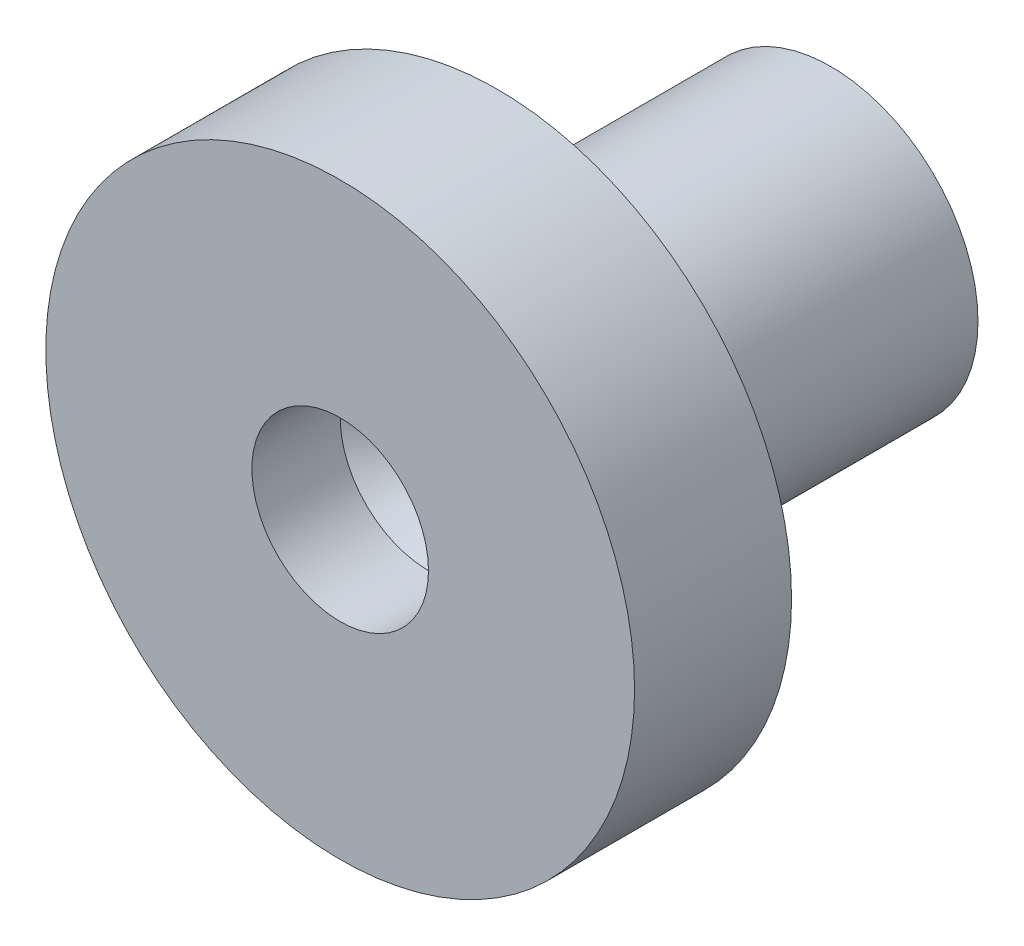
SolidWorks part; units mm, degrees
ref_plane "Спереди" through (0, 0, 0) normal (0, 0, 1) x (1, 0, 0)
ref_plane "Сверху" through (0, 0, 0) normal (0, 1, 0) x (1, 0, 0)
ref_plane "Справа" through (0, 0, 0) normal (1, 0, 0) x (0, 0, -1)
sketch "Эскиз1" plane through (0, 0, 0) normal (0, 0, 1) x (1, 0, 0)
  circle A0 centre (0, 0) radius 4.35
  circle A1 centre (0, 0) radius 7.5
  dimension "D1" = 8.7
  dimension "D2" = 15
extrude "Вытянуть1" add sketch "Эскиз1" along normal blind 17
sketch "Эскиз3" plane through (0, 0, 0) normal (0, 0, -1) x (-1, 0, 0)
  circle A0 centre (0, 0) radius 6
  dimension "D1" = 12
extrude "Вытянуть2" cut sketch "Эскиз3" against normal blind 3
sketch "Эскиз4" plane through (0, 0, 17) normal (0, 0, 1) x (1, 0, 0)
  circle A0 centre (0, 0) radius 7.5
  dimension "D1" = 15
extrude "Вытянуть3" add sketch "Эскиз4" along normal blind 8
sketch "Эскиз5" plane through (0, 0, 25) normal (0, 0, 1) x (1, 0, 0)
  circle A0 centre (0, 0) radius 1.25
  dimension "D1" = 2.5
extrude "Вытянуть4" cut sketch "Эскиз5" against normal mid plane 27
sketch "Эскиз6" plane through (0, 0, 25) normal (0, 0, 1) x (1, 0, 0)
  circle A0 centre (0, 0) radius 4.5
  dimension "D1" = 9
extrude "Вытянуть5" cut sketch "Эскиз6" against normal blind 4.5
sketch "Эскиз7" plane through (0, 0, 20.5) normal (0, 0, 1) x (1, 0, 0)
  circle A0 centre (0, 0) radius 4.5
  dimension "D1" = 9
extrude "Вытянуть6" cut sketch "Эскиз7" against normal blind 2.5 draft 50
sketch "Эскиз8" plane through (0, 0, 25) normal (0, 0, 1) x (1, 0, 0)
  circle A0 centre (0, 0) radius 15
  circle A1 centre (0, 0) radius 7.5
  dimension "D1" = 15
  dimension "D2" = 30
extrude "Вытянуть8" add sketch "Эскиз8" along normal blind 8 from offset 8 offset against normal yes
fillet "Скругление1" radius 3 1 edges at (7.5, 0, 17)
